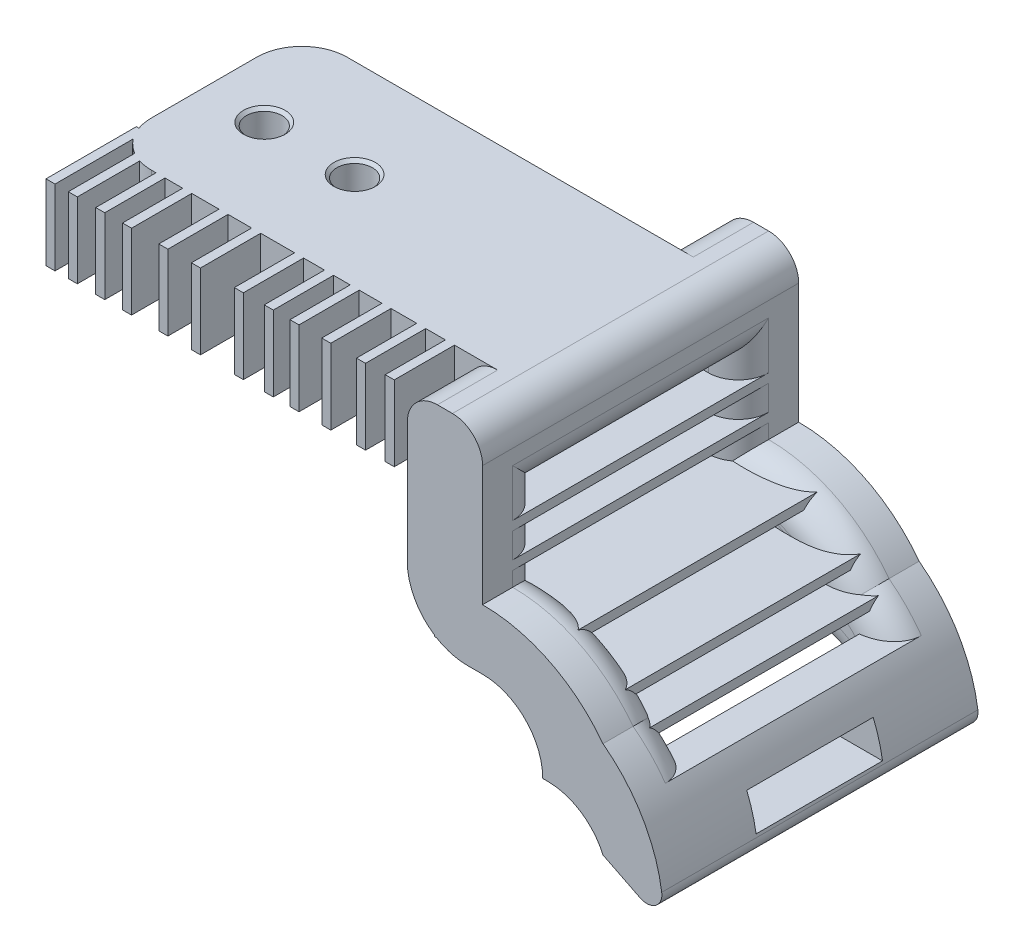
SolidWorks part; units mm, degrees
ref_plane "Front Plane" through (0, 0, 0) normal (0, 0, 1) x (1, 0, 0)
ref_plane "Top Plane" through (0, 0, 0) normal (0, 1, 0) x (1, 0, 0)
ref_plane "Right Plane" through (0, 0, 0) normal (1, 0, 0) x (0, 0, -1)
sketch "Sketch1" plane through (0, 0, 0) normal (0, 1, 0) x (1, 0, 0)
  line L1 (0, 0) -> (36.83, 0)
  line L2 (0, 0) -> (0, 16.51)
  line L3 (0, 16.51) -> (36.83, 16.51)
  line L4 (36.83, 0) -> (36.83, 16.51)
  dimension "D1" = 36.83
  dimension "D2" = 16.51
extrude "Boss-Extrude1" add sketch "Sketch1" along normal blind 6.35
hole_wizard "Ø3.0mm Dowel Hole1" positions "Sketch5" profile "Sketch4" hole size "Ø3.0" standard "ISO" end condition through all
sketch "Sketch5" plane through (0, 6.35, 0) normal (0, 1, 0) x (1, 0, 0)
  line L0 (0, 0) -> (36.83, 0) construction
  line L1 (0, 16.51) -> (0, 0) construction
  point P0 (5.08, 8.255)
  point P2 (12.7, 8.255)
  dimension "D1" = 8.255
  dimension "D2" = 5.08
  dimension "D3" = 7.62
sketch "Sketch4" plane through (5.08, 6.35, -8.255) normal (1, 0, 0) x (0, 0, 1)
  line L0 (0, 0) -> (0, 6.35)
  line L1 (0, 6.35) -> (1.5, 6.35)
  line L2 (1.5, 6.35) -> (1.5, 0)
  line L5 (1.5, 0) -> (0, 0)
  line L11 (0, -6.35) -> (0, 107.95) construction
  dimension "Thru Hole Dia." = 3
  dimension "Thru Hole Depth" = 6.35
chamfer "Chamfer1" distance 0.254 angle 45 4 edges at (12.7, 6.35, -6.755) (5.08, 6.35, -6.755) (5.08, 0, -6.755) (12.7, 0, -6.755)
fillet "Fillet2" radius 3.81 2 edges at (0, 3.175, 0) (0, 3.175, -16.51)
sketch "Sketch14" plane through (0, 0, 0) normal (0, 0, 1) x (1, 0, 0)
  line L1 (36.83, 6.35) -> (30.48, 6.35)
  line L2 (36.83, 6.35) -> (36.83, -11.43)
  line L3 (36.83, -11.43) -> (30.48, -11.43)
  line L4 (30.48, 6.35) -> (30.48, -11.43)
  dimension "D1" = 6.35
  dimension "D2" = 17.78
extrude "Boss-Extrude8" add sketch "Sketch14" along normal blind 5.08
sketch "Sketch15" plane through (0, 0, -16.51) normal (0, 0, -1) x (-1, 0, 0)
  line L1 (-36.83, 6.35) -> (-30.48, 6.35)
  line L2 (-36.83, 6.35) -> (-36.83, -11.43)
  line L3 (-36.83, -11.43) -> (-30.48, -11.43)
  line L4 (-30.48, 6.35) -> (-30.48, -11.43)
  dimension "D1" = 17.78
  dimension "D2" = 6.35
extrude "Boss-Extrude9" add sketch "Sketch15" along normal blind 5.08
sketch "Sketch16" plane through (36.83, 0, 0) normal (1, 0, 0) x (0, 0, -1)
  line L0 (0, -11.43) -> (0, 0) construction
  line L1 (-5.08, -11.43) -> (0, -11.43)
  line L2 (-5.08, -11.43) -> (-5.08, -6.35)
  line L3 (-5.08, -6.35) -> (0, -6.35)
  line L4 (0, -11.43) -> (0, -6.35)
  line L5 (21.59, 6.35) -> (21.59, -11.43) construction
  line L6 (16.51, -11.43) -> (21.59, -11.43)
  line L7 (16.51, -11.43) -> (16.51, -6.35)
  line L8 (16.51, -6.35) -> (21.59, -6.35)
  line L9 (21.59, -11.43) -> (21.59, -6.35)
  dimension "D1" = 5.08
  dimension "D2" = 5.08
extrude "Boss-Extrude10" add sketch "Sketch16" along normal blind 10.16
sketch "Sketch18" plane through (0, -11.43, 0) normal (0, -1, 0) x (1, 0, 0)
  line L0 (30.48, 0) -> (46.99, 0) construction
  line L1 (46.99, 5.08) -> (41.91, 5.08)
  line L2 (46.99, 5.08) -> (46.99, 0)
  line L3 (46.99, 0) -> (41.91, 0)
  line L4 (41.91, 5.08) -> (41.91, 0)
  line L5 (46.99, -21.59) -> (30.48, -21.59) construction
  line L6 (46.99, -16.51) -> (41.91, -16.51)
  line L7 (46.99, -16.51) -> (46.99, -21.59)
  line L8 (46.99, -21.59) -> (41.91, -21.59)
  line L9 (41.91, -16.51) -> (41.91, -21.59)
  dimension "D1" = 5.08
  dimension "D2" = 5.08
extrude "Boss-Extrude12" add sketch "Sketch18" along normal blind 5.08
sketch "Sketch19" plane through (46.99, 0, 0) normal (1, 0, 0) x (0, 0, -1)
  line L0 (0, -16.51) -> (0, -6.35) construction
  line L1 (-5.08, -16.51) -> (0, -16.51)
  line L2 (-5.08, -16.51) -> (-5.08, -11.43)
  line L3 (-5.08, -11.43) -> (0, -11.43)
  line L4 (0, -16.51) -> (0, -11.43)
  line L5 (21.59, -16.51) -> (21.59, -6.35) construction
  line L6 (16.51, -16.51) -> (21.59, -16.51)
  line L7 (16.51, -16.51) -> (16.51, -11.43)
  line L8 (16.51, -11.43) -> (21.59, -11.43)
  line L9 (21.59, -16.51) -> (21.59, -11.43)
extrude "Boss-Extrude13" add sketch "Sketch19" along normal blind 5.08
sketch "Sketch20" plane through (0, -16.51, 0) normal (0, -1, 0) x (1, 0, 0)
  line L0 (41.91, 0) -> (52.07, 0) construction
  line L1 (52.07, 5.08) -> (46.99, 5.08)
  line L2 (52.07, 5.08) -> (52.07, 0)
  line L3 (52.07, 0) -> (46.99, 0)
  line L4 (46.99, 5.08) -> (46.99, 0)
  line L5 (41.91, -21.59) -> (52.07, -21.59) construction
  line L6 (52.07, -16.51) -> (46.99, -16.51)
  line L7 (52.07, -16.51) -> (52.07, -21.59)
  line L8 (52.07, -21.59) -> (46.99, -21.59)
  line L9 (46.99, -16.51) -> (46.99, -21.59)
extrude "Boss-Extrude14" add sketch "Sketch20" along normal blind 5.588
sketch "Sketch21" plane through (0, 0, -21.59) normal (0, 0, -1) x (-1, 0, 0)
  line L0 (-46.99, -22.098) -> (-52.07, -22.098)
  line L1 (-52.07, -22.098) -> (-46.99, -19.558)
  line L2 (-46.99, -22.098) -> (-46.99, -16.51) construction
  line L3 (-46.99, -19.558) -> (-46.99, -22.098)
  dimension "D1" = 2.54
extrude "Cut-Extrude5" cut sketch "Sketch21" against normal through all
sketch "Sketch22" plane through (0, 0, -16.51) normal (0, 0, 1) x (1, 0, 0)
  line L0 (52.07, -22.098) -> (46.99, -19.558)
  line L1 (46.99, -19.558) -> (46.99, -14.224)
  line L2 (46.99, -14.224) -> (52.07, -14.224)
  line L3 (52.07, -11.43) -> (52.07, -22.098) construction
  line L4 (52.07, -14.224) -> (52.07, -22.098)
  dimension "D1" = 7.874
extrude "Boss-Extrude15" add sketch "Sketch22" along normal blind 16.51
sketch "Sketch23" plane through (46.99, 0, 0) normal (-1, 0, 0) x (0, 0, 1)
  line L0 (5.08, -19.558) -> (-21.59, -19.558) construction
  line L1 (-13.589, -19.558) -> (-2.921, -19.558)
  line L2 (-13.589, -19.558) -> (-13.589, -16.764)
  line L3 (-13.589, -16.764) -> (-2.921, -16.764)
  line L4 (-2.921, -19.558) -> (-2.921, -16.764)
  line L6 (0, -14.224) -> (-16.51, -14.224) construction
  point P6 (-8.255, -14.224)
  dimension "D1" = 2.794
  dimension "D2" = 10.668
  dimension "D3" = 5.334
extrude "Cut-Extrude6" cut sketch "Sketch23" against normal blind 16.51
fillet "Fillet3" radius 12.7 3 edges at (52.07, -11.43, -19.05) (46.99, -6.35, -19.05) (46.99, -6.35, 2.54)
fillet "Fillet4" radius 5.08 6 edges at (30.48, -11.43, -19.05) (30.48, -11.43, 2.54)
fillet "Fillet5" radius 1.27 1 edges
fillet "Fillet6" radius 2.54 20 edges at (40.4221, -12.9179, -16.51) (31.9679, -9.9421, -16.51) (40.4221, -12.9179, 0) (31.9679, -9.9421, 0) (30.48, 6.35, 2.54) (30.48, 6.35, -19.05) (36.83, 0, -8.255) (36.83, 6.35, -8.255) (48.4608, -12.7217, -16.51) (42.5096, -7.6908, -16.51) (48.4608, -12.7217, 0) (45.1165, -17.3398, 0) (45.1165, -17.3398, -16.51) (30.48, -3.175, -16.51) (30.48, -3.175, 0) (36.83, -3.175, -16.51)
sketch "Sketch25" plane through (0, 0, 0) normal (0, 0, 1) x (1, 0, 0)
  line L0 (3.81, 6.35) -> (33.02, 6.35) construction
  line L1 (28.6182, 6.35) -> (29.3802, 6.35)
  line L2 (28.6182, 6.35) -> (28.6182, 0)
  line L3 (28.6182, 0) -> (29.3802, 0)
  line L4 (29.3802, 6.35) -> (29.3802, 0)
  line L5 (3.81, 0) -> (30.48, 0) construction
  line L7 (26.1943, 6.35) -> (26.9563, 6.35)
  line L8 (26.1943, 6.35) -> (26.1943, 0)
  line L9 (26.1943, 0) -> (26.9563, 0)
  line L10 (26.9563, 6.35) -> (26.9563, 0)
  line L11 (23.2635, 6.35) -> (24.0255, 6.35)
  line L12 (23.2635, 6.35) -> (23.2635, 0)
  line L13 (23.2635, 0) -> (24.0255, 0)
  line L14 (24.0255, 6.35) -> (24.0255, 0)
  line L15 (18.415, 6.35) -> (19.177, 6.35)
  line L16 (18.415, 6.35) -> (18.415, 0)
  line L17 (18.415, 0) -> (19.177, 0)
  line L18 (19.177, 6.35) -> (19.177, 0)
  line L19 (20.5821, 6.35) -> (21.3441, 6.35)
  line L20 (20.5821, 6.35) -> (20.5821, 0)
  line L21 (20.5821, 0) -> (21.3441, 0)
  line L22 (21.3441, 6.35) -> (21.3441, 0)
  line L23 (15.8893, 6.35) -> (16.6513, 6.35)
  line L24 (15.8893, 6.35) -> (15.8893, 0)
  line L25 (15.8893, 0) -> (16.6513, 0)
  line L26 (16.6513, 6.35) -> (16.6513, 0)
  line L27 (12.2686, 6.35) -> (13.0306, 6.35)
  line L28 (12.2686, 6.35) -> (12.2686, 0)
  line L29 (12.2686, 0) -> (13.0306, 0)
  line L30 (13.0306, 6.35) -> (13.0306, 0)
  line L31 (9.5169, 6.35) -> (10.2789, 6.35)
  line L32 (9.5169, 6.35) -> (9.5169, 0)
  line L33 (9.5169, 0) -> (10.2789, 0)
  line L34 (10.2789, 6.35) -> (10.2789, 0)
  line L35 (6.4534, 6.35) -> (7.2154, 6.35)
  line L36 (6.4534, 6.35) -> (6.4534, 0)
  line L37 (6.4534, 0) -> (7.2154, 0)
  line L38 (7.2154, 6.35) -> (7.2154, 0)
  line L39 (4.1965, 6.35) -> (4.9585, 6.35)
  line L40 (4.1965, 6.35) -> (4.1965, 0)
  line L41 (4.1965, 0) -> (4.9585, 0)
  line L42 (4.9585, 6.35) -> (4.9585, 0)
  line L43 (1.8813, 6.35) -> (2.6433, 6.35)
  line L44 (1.8813, 6.35) -> (1.8813, 0)
  line L45 (1.8813, 0) -> (2.6433, 0)
  line L46 (2.6433, 6.35) -> (2.6433, 0)
  line L47 (0, 0) -> (0.762, 0)
  line L48 (0, 0) -> (0, 6.35)
  line L49 (0, 6.35) -> (0.762, 6.35)
  line L50 (0.762, 0) -> (0.762, 6.35)
  dimension "D1" = 0.762
  dimension "D2" = 0.762
  dimension "D3" = 0.762
  dimension "D4" = 0.762
  dimension "D5" = 0.762
  dimension "D6" = 0.762
  dimension "D7" = 0.762
  dimension "D8" = 0.762
  dimension "D9" = 0.762
  dimension "D10" = 0.762
  dimension "D11" = 0.762
  dimension "D12" = 0.762
extrude "Boss-Extrude16" add sketch "Sketch25" along normal blind 5.08 and the other way blind 2.54
sketch "Sketch28" plane through (0, 0, 5.08) normal (0, 0, 1) x (1, 0, 0)
  line L0 (36.83, -6.35) -> (36.83, 3.81) construction
  line L1 (36.83, -2.2352) -> (30.48, -2.2352)
  line L2 (36.83, -2.2352) -> (36.83, -1.4732)
  line L3 (36.83, -1.4732) -> (30.48, -1.4732)
  line L4 (30.48, -2.2352) -> (30.48, -1.4732)
  line L5 (30.48, 3.81) -> (30.48, -6.35) construction
  line L7 (36.83, -5.1191) -> (30.48, -5.1191)
  line L8 (36.83, -5.1191) -> (36.83, -4.3571)
  line L9 (36.83, -4.3571) -> (30.48, -4.3571)
  line L10 (30.48, -5.1191) -> (30.48, -4.3571)
  line L11 (47.244, -12.7391) -> (40.386, -12.7391)
  line L12 (47.244, -12.7391) -> (47.244, -11.9771)
  line L13 (47.244, -11.9771) -> (40.386, -11.9771)
  line L14 (40.386, -12.7391) -> (40.386, -11.9771)
  line L15 (32.766, -10.7071) -> (45.466, -10.7071)
  line L16 (32.766, -10.7071) -> (32.766, -9.9451)
  line L17 (32.766, -9.9451) -> (45.466, -9.9451)
  line L18 (45.466, -10.7071) -> (45.466, -9.9451)
  line L19 (30.988, -7.4051) -> (41.656, -7.4051)
  line L20 (30.988, -7.4051) -> (30.988, -8.1671)
  line L21 (30.988, -8.1671) -> (41.656, -8.1671)
  line L22 (41.656, -7.4051) -> (41.656, -8.1671)
  dimension "D1" = 0.762
  dimension "D2" = 0.762
  dimension "D3" = 0.762
  dimension "D4" = 0.762
  dimension "D5" = 0.762
  dimension "D6" = 2.286
  dimension "D7" = 1.778
  dimension "D8" = 1.27
  dimension "D9" = 0.508
  dimension "D10" = 10.668
  dimension "D11" = 1.778
  dimension "D12" = 12.7
  dimension "D13" = 7.62
  dimension "D14" = 6.858
extrude "Boss-Extrude17" add sketch "Sketch28" against normal blind 25.4
